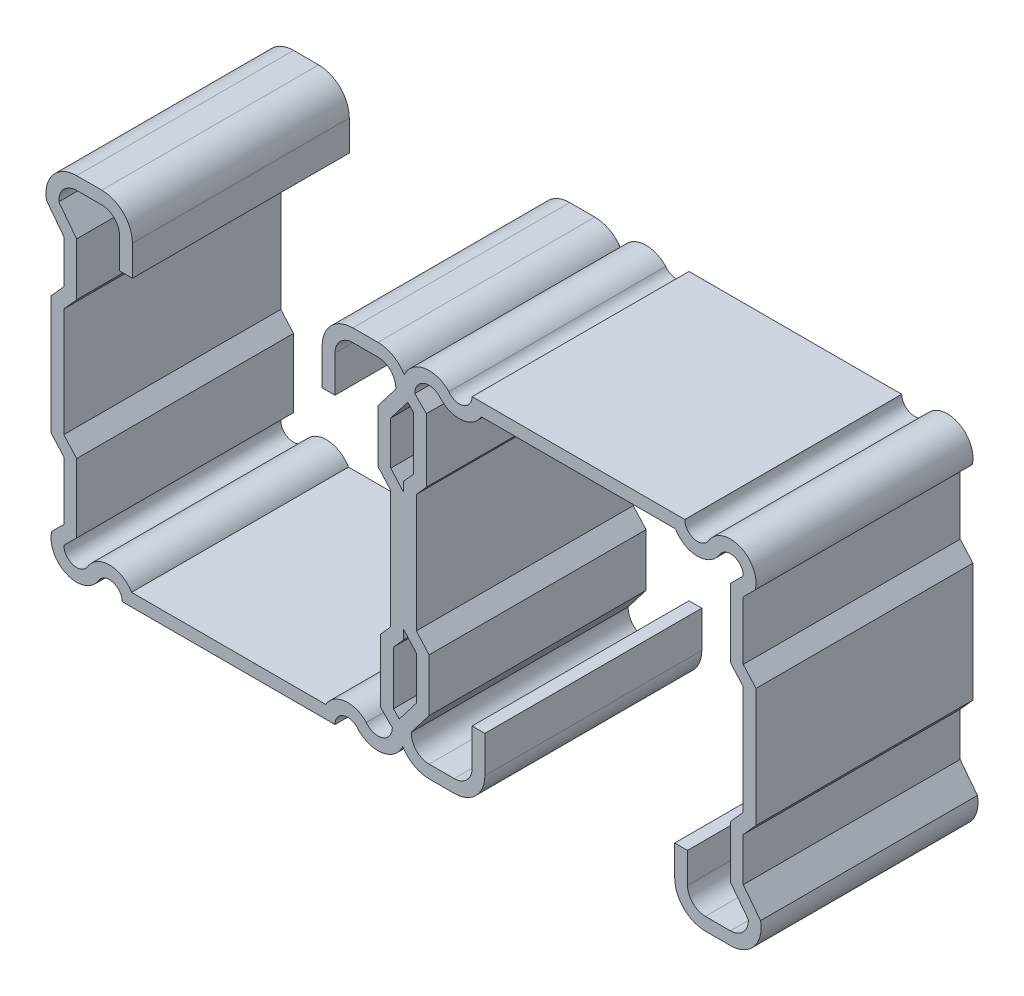
SolidWorks part; units mm, degrees
note: '?' marks a value the reader was unsure of.
ref_plane "Plane1" through (0, 0, 0) normal (0, 0, 1) x (1, 0, 0)
ref_plane "Plane2" through (0, 0, 0) normal (0, 1, 0) x (1, 0, 0)
ref_plane "Plane3" through (0, 0, 0) normal (1, 0, 0) x (0, 0, -1)
sketch "Sketch1" plane through (-20.32, 17.78, 0) normal (0, 0, 1) x (1, 0, 0)
  line L0 (17.3228, 17.0759) -> (19.4124, 19.8001)
  line L1 (17.6403, -13.3787) -> (19.0032, -14.7415)
  line L2 (-17.9578, -13.9795) -> (-19.4564, -15.4781)
  line L4 (-17.9578, -13.9795) -> (-17.9578, -5.9368)
  line L5 (17.3228, 21.9964) -> (14.3858, 21.9964)
  line L6 (12.2936, 19.9042) -> (12.2936, 15.6146)
  line L7 (-17.9578, -5.9368) -> (-19.4564, -4.2539)
  line L8 (-12.9286, 19.1676) -> (-12.9286, 15.6146)
  line L10 (-19.4564, -4.2539) -> (-19.4564, 8.4957)
  line L11 (-17.9578, 10.1786) -> (-19.4564, 8.4957)
  line L12 (-17.9578, 10.1786) -> (-17.9578, 16.3393)
  line L13 (-17.9578, 16.3393) -> (-20.0474, 19.0635)
  line L14 (-17.9578, 21.2598) -> (-15.0208, 21.2598)
  line L16 (17.6403, -13.3787) -> (17.6403, -5.9368)
  line L17 (17.3228, 10.9152) -> (17.3228, 17.0759)
  line L18 (-11.43, 19.1676) -> (-11.43, 15.6146)
  line L19 (-17.9578, 22.7584) -> (-15.0208, 22.7584)
  line L20 (-19.4564, 15.8307) -> (-21.4799, 18.4689)
  line L21 (-19.4564, 10.7491) -> (-19.4564, 15.8307)
  line L22 (-19.4564, 10.7491) -> (-20.955, 9.0662)
  line L23 (-20.955, -4.8244) -> (-20.955, 9.0662)
  line L24 (-19.4564, -6.5073) -> (-20.955, -4.8244)
  line L25 (18.8214, -4.6104) -> (18.8214, 9.2323)
  line L26 (-19.4564, -13.3588) -> (-19.4564, -6.5073)
  line L27 (-19.4564, -13.3588) -> (-20.871, -14.7733)
  line L28 (10.795, 19.9042) -> (10.795, 15.6146)
  line L29 (17.3228, 23.495) -> (14.3858, 23.495)
  line L30 (18.8214, 16.5673) -> (20.8449, 19.2055)
  line L31 (18.8214, 11.4857) -> (18.8214, 16.5673)
  line L32 (18.8214, 11.4857) -> (20.32, 9.8028)
  line L33 (20.32, -5.181) -> (20.32, 9.8028)
  line L34 (19.1389, -6.5073) -> (20.32, -5.181)
  line L35 (19.1389, -12.7579) -> (19.1389, -6.5073)
  line L36 (19.1389, -12.7579) -> (20.4241, -14.0431)
  line L37 (17.6403, -5.9368) -> (18.8214, -4.6104)
  line L38 (-12.6128, -17.78) -> (12.2953, -17.78)
  line L39 (17.3228, 10.9152) -> (18.8214, 9.2323)
  line L41 (-11.5242, -16.2814) -> (11.2067, -16.2814)
  line L42 (-12.9286, 15.6146) -> (-11.43, 15.6146)
  line L43 (10.795, 15.6146) -> (12.2936, 15.6146)
  arc A0 (19.0032, -14.7415) -> (15.9562, -15.7193) centre (17.3228, -14.7415) cw
  arc A1 (15.9562, -15.7193) -> (11.2067, -16.2814) centre (13.7938, -17.7947) ccw
  arc A2 (-16.7318, -16.3399) -> (-11.5242, -16.2814) centre (-14.1113, -17.7947) cw
  arc A3 (-19.4564, -15.4781) -> (-16.7318, -16.3399) centre (-17.9578, -15.4781) ccw
  arc A4 (-17.9578, 21.2598) -> (-20.0474, 19.0635) centre (-17.9578, 19.1676) ccw
  arc A5 (-12.9286, 19.1676) -> (-15.0208, 21.2598) centre (-15.0208, 19.1676) ccw
  arc A6 (17.3228, 21.9964) -> (19.4124, 19.8001) centre (17.3228, 19.9042) cw
  arc A7 (12.2936, 19.9042) -> (14.3858, 21.9964) centre (14.3858, 19.9042) cw
  arc A8 (-11.43, 19.1676) -> (-15.0208, 22.7584) centre (-15.0208, 19.1676) ccw
  arc A9 (-17.9578, 22.7584) -> (-21.4799, 18.4689) centre (-17.9578, 19.1676) ccw
  arc A10 (-20.871, -14.7733) -> (-15.3373, -16.9329) centre (-17.9578, -15.4781) ccw
  arc A11 (10.795, 19.9042) -> (14.3858, 23.495) centre (14.3858, 19.9042) cw
  arc A12 (17.3228, 23.495) -> (20.8449, 19.2055) centre (17.3228, 19.9042) cw
  arc A13 (20.4241, -14.0431) -> (15.0198, -16.9329) centre (17.3228, -14.7415) cw
  arc A14 (15.0198, -16.9329) -> (12.2953, -17.78) centre (13.7938, -17.7947) ccw
  arc A15 (-15.3373, -16.9329) -> (-12.6128, -17.78) centre (-14.1113, -17.7947) cw
  dimension "D1" = 41.275
  dimension "D9" = 7.1437
  dimension "D2" = 34.6458
  dimension "D4" = 22.225
  dimension "D3" = 36.9623
  dimension "D5" = 9.525
  dimension "D12" = 41.275
  dimension "D14" = 13.6922
extrude "Base-Extrude" add sketch "Sketch1" along normal mid plane 25.4
ref_plane "Plane4" through (0, 20.6375, 0) normal (0, 1, 0) x (-1, 0, 0)
ref_axis "Axis1" through (0, 20.6375, 50) along (0, 0, -1)?
pattern_circular "CirPattern1" count 2 every 180 about axis through (0, 20.6375, 0) along (0, 0, 1) of "Base-Extrude"
